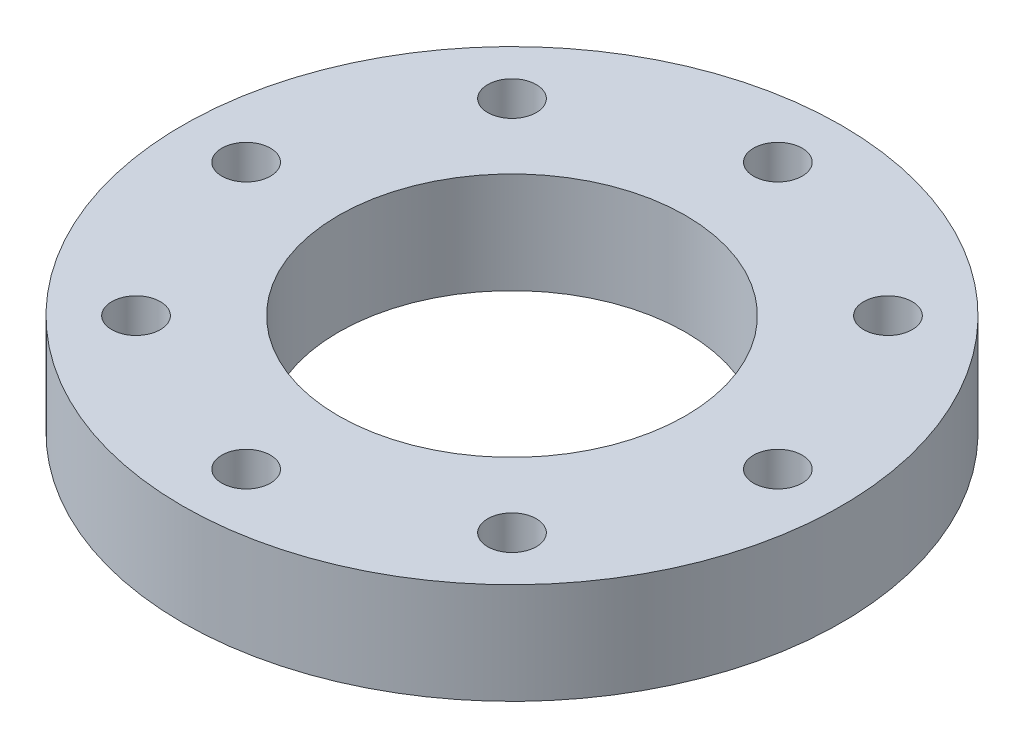
SolidWorks part; units mm, degrees
ref_plane "Front Plane" through (0, 0, 0) normal (0, 0, 1) x (1, 0, 0)
ref_plane "Top Plane" through (0, 0, 0) normal (0, 1, 0) x (1, 0, 0)
ref_plane "Right Plane" through (0, 0, 0) normal (1, 0, 0) x (0, 0, -1)
sketch "Sketch1" plane through (0, 0, 0) normal (0, 1, 0) x (1, 0, 0)
  circle A0 centre (0, 0) radius 57.15
  dimension "D1" = 114.3
extrude "Extrude-Thin1" add sketch "Sketch1" along normal blind 17.526 thin thin type one direction reverse wall 27.051
sketch "Sketch2" plane through (0, 0, 0) normal (0, 1, 0) x (1, 0, 0)
  circle A0 centre (0, 46.101) radius 4.2164
extrude "Cut-Extrude2" cut sketch "Sketch2" along normal blind 17.526
ref_axis "Axis1" through (0, 58.677, 0) along (0, -1, 0)
pattern_circular "CirPattern1" count 8 over 360 about axis through (0, 58.677, 0) along (0, -1, 0) of "Cut-Extrude2"
sketch "Sketch4" plane through (0, 0, 0) normal (0, 1, 0) x (1, 0, 0)
  line L0 (0, 0) -> (0, 46.8507)
ref_plane "Plane1" through (0, 0, 0) normal (0, -1, 0) x (1, 0, 0)
sketch "Sketch5" plane through (0, 0, 0) normal (0, -1, 0) x (1, 0, 0)
  circle A0 centre (0, 0) radius 45.72
  dimension "D1" = 91.44
extrude "Extrude1" [suppressed] add sketch "Sketch5" along normal blind 144.526
